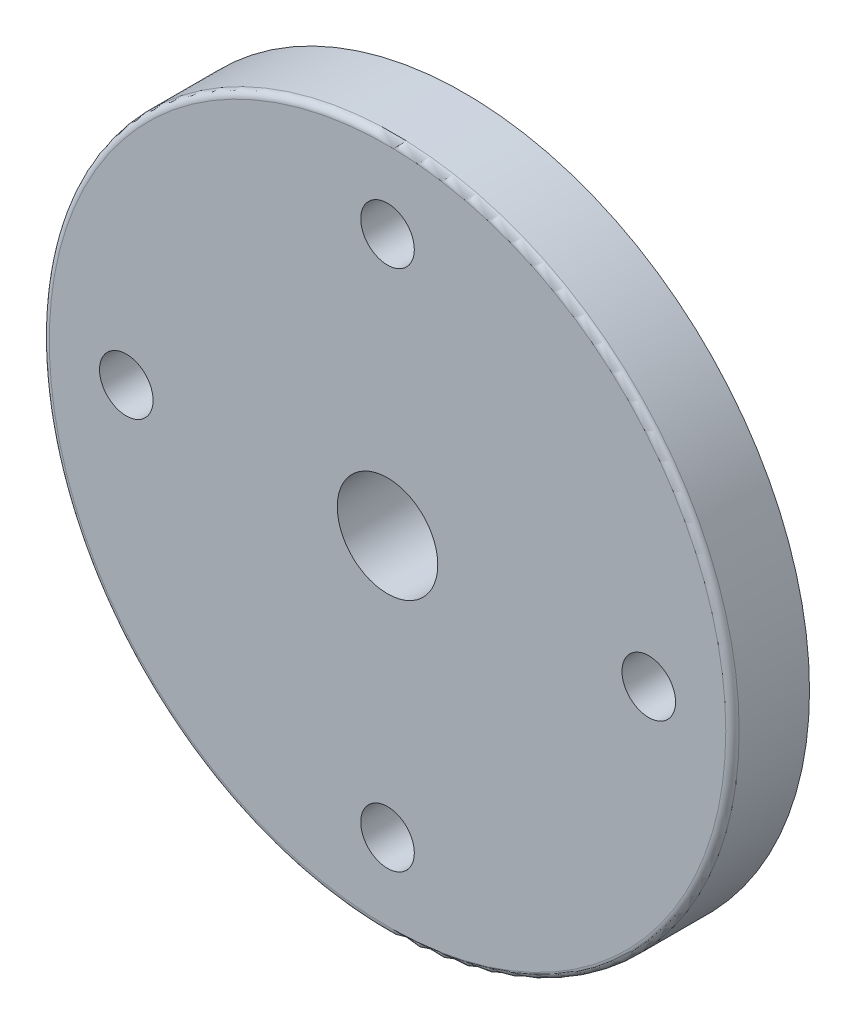
SolidWorks part; units mm, degrees
ref_plane "Front Plane" through (0, 0, 0) normal (0, 0, 1) x (1, 0, 0)
ref_plane "Top Plane" through (0, 0, 0) normal (0, 1, 0) x (1, 0, 0)
ref_plane "Right Plane" through (0, 0, 0) normal (1, 0, 0) x (0, 0, -1)
ref_plane "Plane1" through (0, 0, -2.5) normal (0, 0, -1) x (-1, 0, 0)
sketch "Sketch1" plane through (0, 0, -2.5) normal (0, 0, -1) x (-1, 0, 0)
  circle A0 centre (0, 0) radius 10.3
  dimension "D1" = 20.6
extrude "Boss-Extrude1" add sketch "Sketch1" against normal blind 2.3
sketch "Sketch2" plane through (0, 0, -2.5) normal (0, 0, -1) x (-1, 0, 0)
  circle A0 centre (0, 0) radius 4.375
  dimension "D1" = 8.75
extrude "Boss-Extrude2" add sketch "Sketch2" along normal blind 3.2
sketch "Sketch3" plane through (0, 0, -5.7) normal (0, 0, -1) x (-1, 0, 0)
  circle A0 centre (0, 0) radius 3
  dimension "D1" = 6
extrude "Cut-Extrude1" cut sketch "Sketch3" against normal blind 2.75
sketch "Sketch4" plane through (0, 0, -0.2) normal (0, 0, 1) x (1, 0, 0)
  circle A0 centre (0, 0) radius 1.5
extrude "Cut-Extrude2" cut sketch "Sketch4" against normal through all
sketch "Sketch12" plane through (0, 0, -2.5) normal (0, 0, -1) x (-1, 0, 0)
  circle A0 centre (0, 7.8) radius 0.8
  circle A1 centre (0, 0) radius 7.8 construction
  circle A2 centre (7.8, 0) radius 0.8
  circle A3 centre (0, -7.8) radius 0.8
  circle A4 centre (-7.8, 0) radius 0.8
  point P14 (0, 0)
  dimension "D1" = 1.6
  dimension "D2" = 15.6
  dimension "D3" = 4
extrude "Cut-Extrude10" cut sketch "Sketch12" against normal through all
fillet "Fillet2" radius 0.2 1 edges at (10.3, 0, -0.2) tangent propagation no
fillet "Fillet3" radius 0.3 1 edges at (-4.375, 0, -5.7)
